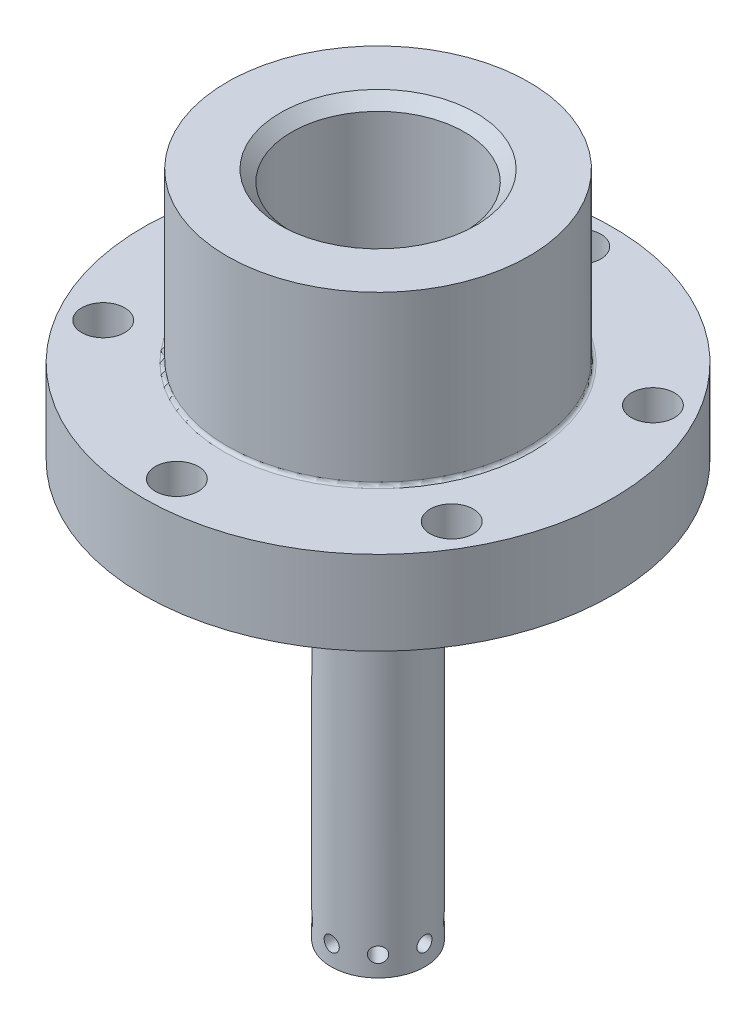
SolidWorks part; units mm, degrees
ref_plane "Front Plane" through (0, 0, 0) normal (0, 0, 1) x (1, 0, 0)
ref_plane "Top Plane" through (0, 0, 0) normal (0, 1, 0) x (1, 0, 0)
ref_plane "Right Plane" through (0, 0, 0) normal (1, 0, 0) x (0, 0, -1)
sketch "Sketch1" plane through (0, 0, 0) normal (0, 0, 1) x (1, 0, 0)
  line L0 (-3.556, -2.0672) -> (-1.524, -2.0672)
  line L1 (0, 8.2157) -> (0, -2.0672) construction
  line L2 (-3.556, 23.0788) -> (-1.524, 23.0788)
  line L3 (-3.556, -2.0672) -> (-3.556, 23.0788)
  line L7 (-1.524, 23.0788) -> (-1.524, -2.0672)
  dimension "D2" = 3.556
  dimension "D3" = 1.524
  dimension "D4" = 25.146
revolve "Revolve2" add sketch "Sketch1" angle 360 about L1 region at (-2.54, 10.5058, 0)
ref_plane "Plane1" through (-3.556, 0, 0) normal (-1, 0, 0) x (0, 0, 1)
sketch "Sketch2" plane through (-3.556, 0, 0) normal (-1, 0, 0) x (0, 0, 1)
  line L5 (-3.556, -2.0672) -> (3.556, -2.0672) construction
  line L6 (-3.556, -2.0672) -> (3.556, -2.0672) construction
  circle A0 centre (0.0002, -0.5432) radius 0.5715
  dimension "HoleDiam" = 1.143
  dimension "WeldHeightSquare" = 1.524
extrude "Cut-Extrude1" cut sketch "Sketch2" against normal up to next contours A0
ref_axis "Axis2" through (0, -2.0672, 0) along (0, 1, 0)
pattern_circular "CirPattern1" count 8 over 360 about axis through (0, -2.0672, 0) along (0, 1, 0) of "Cut-Extrude1"
ref_plane "Plane2" through (0, 23.0788, 0) normal (0, -1, 0) x (-1, 0, 0)
sketch "Sketch3" plane through (0, 23.0788, 0) normal (0, -1, 0) x (-1, 0, 0)
  circle A0 centre (0, 0) radius 1.524 construction
  circle A1 centre (0, 0) radius 3.556 construction
  circle A2 centre (0, 0) radius 1.524
  circle A3 centre (0, 0) radius 3.556
extrude "Boss-Extrude1" add sketch "Sketch3" against normal blind 6.35
ref_plane "Plane3" through (0, 29.4288, 0) normal (0, 1, 0) x (1, 0, 0)
sketch "Sketch4" plane through (0, 29.4288, 0) normal (0, 1, 0) x (1, 0, 0)
  circle A0 centre (0, 0) radius 17.78
  circle A1 centre (0, 0) radius 1.524
  dimension "D2" = 17.78
extrude "Boss-Extrude2" add sketch "Sketch4" along normal blind 6.35
sketch "Sketch11" plane through (0, 35.7788, 0) normal (0, 1, 0) x (1, 0, 0)
  line L0 (0, 0) -> (0, -15.24) construction
  circle A0 centre (0, -15.24) radius 1.6319
  circle A1 centre (0, 0) radius 15.24 construction
  dimension "D2" = 3.2639
extrude "Cut-Extrude2" cut sketch "Sketch11" against normal up to next
ref_axis "Axis1" through (0, -2.0672, 0) along (0, 1, 0)
pattern_circular "CirPattern2" count 6 over 360 about axis through (0, -2.0672, 0) along (0, 1, 0) of "Cut-Extrude2"
chamfer "Chamfer1" distance 3.048 angle 60 1 edges at (0, 35.7788, 1.524) first distance on face at (-14.6115, 35.7788, 8.436)
sketch "Sketch13" plane through (0, 35.7788, 0) normal (0, 1, 0) x (1, 0, 0)
  circle A0 centre (0, 0) radius 6.5481
  circle A1 centre (0, 0) radius 11.43
extrude "Boss-Extrude4" add sketch "Sketch13" along normal blind 12.7
fillet "Fillet4" radius 0.254 1 edges at (0, 35.7788, 11.43)
chamfer "Chamfer2" distance 0.8517 distance2 0.8395 1 edges at (0, 48.4788, 6.5481) first distance on face at (0, 48.4788, 11.43)
sketch "Sketch14" plane through (0, 35.7788, 0) normal (0, 1, 0) x (1, 0, 0)
  circle A0 centre (-13.1982, -7.62) radius 2.794
sketch "Sketch15" plane through (0, 29.4288, 0) normal (0, -1, 0) x (1, 0, 0)
  circle A0 centre (0, 0) radius 4.699
  circle A1 centre (0, 0) radius 3.556
extrude "Boss-Extrude5" add sketch "Sketch15" along normal blind 6.35
equation "\"ManifoldThickness\"= 0.250"
equation "\"D1@Boss-Extrude1\"=\"ManifoldThickness\""
equation "\"SkipDistance\"= \"OD\"'equal to pintle OD"
equation "\"OD\"= 0.280"
equation "\"AnnulusLength\"= 0.29"
equation "\"ManifoldChamberThickness\"= 0.35"
equation "\"D4@Sketch1\"=\"SkipDistance\"+\"AnnulusLength\"+\"ManifoldChamberThickness\"+\"HoleHeight\"+\"WeldHeight\""
equation "\"HoleHeight\"= 0.035"
equation "\"D2@Sketch1\"=\"OD\"/2"
equation "\"IR\"=0.06"
equation "\"D3@Sketch1\" = \"IR\""
equation "\"ID\"= \"IR\" * 2"
equation "\"440loose\"= 0.1285"
equation "\"D2@Sketch11\"=\"440loose\""
equation "\"ManifoldPlateThickness\"= 0.25"
equation "\"WeldHeight\"=0.035"
